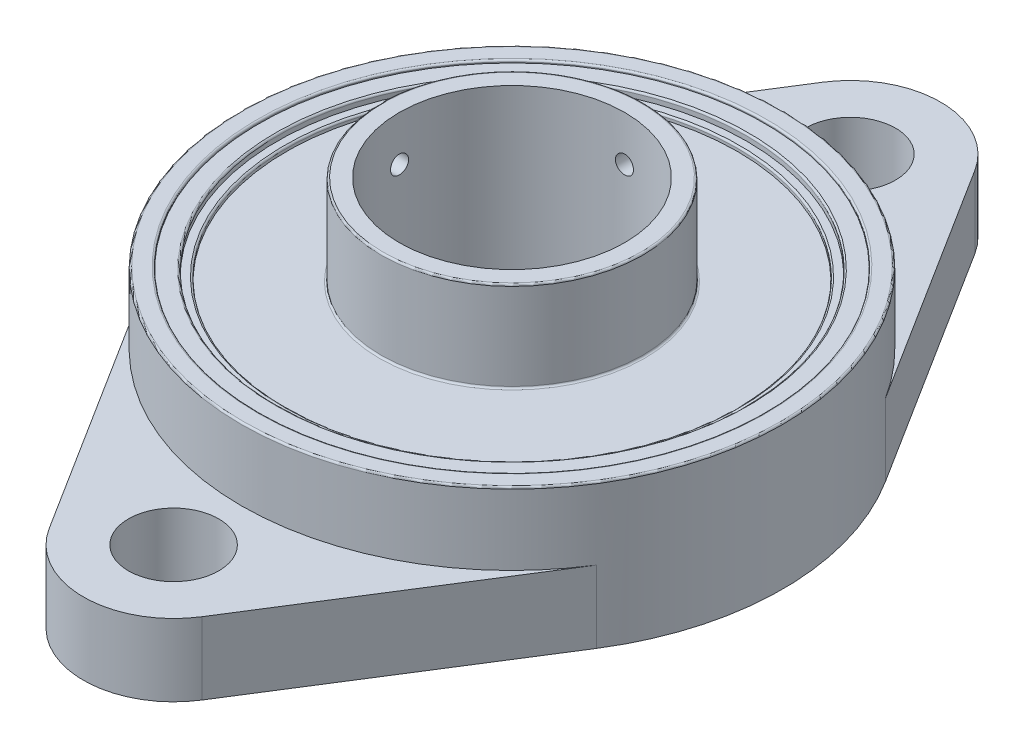
SolidWorks part; units mm, degrees
ref_plane "Front Plane" through (0, 0, 0) normal (0, 0, 1) x (1, 0, 0)
ref_plane "Top Plane" through (0, 0, 0) normal (0, 1, 0) x (1, 0, 0)
ref_plane "Right Plane" through (0, 0, 0) normal (1, 0, 0) x (0, 0, -1)
sketch "Sketch1" plane through (0, 0, 0) normal (0, 1, 0) x (1, 0, 0)
  line L0 (0, -47.5) -> (0, 47.5) construction
  line L1 (0, 0) -> (-50000, 0) construction
  line L2 (25.3772, -16) -> (8.4591, -42.8333)
  line L3 (25.3772, 16) -> (8.4591, 42.8333)
  line L4 (-25.3772, -16) -> (-8.4591, -42.8333)
  line L5 (-25.3772, 16) -> (-8.4591, 42.8333)
  circle A0 centre (0, 0) radius 30
  circle A1 centre (0, 0) radius 12.5
  circle A2 centre (0, 37.5) radius 5
  circle A3 centre (0, 0) radius 28
  circle A4 centre (0, 0) radius 14.5
  arc A5 (8.4591, 42.8333) -> (-8.4591, 42.8333) centre (0, 37.5) ccw
  circle A6 centre (0, -37.5) radius 5
  arc A7 (-8.4591, -42.8333) -> (8.4591, -42.8333) centre (0, -37.5) ccw
  circle A8 centre (0, 0) radius 26
  circle A9 centre (0, 0) radius 25
  point P6 (0, 0)
  dimension "D1" = 25
  dimension "D2" = 60
  dimension "D5" = 10
  dimension "D3" = 95
  dimension "D4" = 75
  dimension "D6" = 2
  dimension "D7" = 2
  dimension "D8" = 2
  dimension "D9" = 1
extrude "A1" add sketch "Sketch1" along normal blind 8 contours L4 A7 L2 A0 A6 | A0 A3 | L3 A5 L5 A0 A2 region at (16.4128, 0, 29.0981) region at (0, 0, 29.1515) region at (-16.4128, 0, -29.0981)
extrude "A" add sketch "Sketch1<3>" along normal blind 16 contours A0 A3 region at (0, 0, 29.1515)
sketch "Sketch1<3>" plane through (0, 0, 0) normal (0, 1, 0) x (1, 0, 0) same geometry as "Sketch1"
extrude "A0" add sketch "Sketch1<4>" along normal blind 24.5 contours A4 A1 region at (-14.0899, 0, 0)
sketch "Sketch1<4>" plane through (0, 0, 0) normal (0, 1, 0) x (1, 0, 0) same geometry as "Sketch1"
extrude "Bearing outer d" add sketch "Sketch1<7>" along normal blind 13 from offset 2 separate body contours A8 A9 region at (-25.2646, 0, 0)
sketch "Sketch1<7>" plane through (0, 0, 0) normal (0, 1, 0) x (1, 0, 0) same geometry as "Sketch1"
extrude "Boss-Extrude6" add sketch "Sketch1<8>" along normal blind 14.5 from offset 1.2 contours A3 A8 region at (-27.208, 0, 0)
sketch "Sketch1<8>" plane through (0, 0, 0) normal (0, 1, 0) x (1, 0, 0) same geometry as "Sketch1"
extrude "Boss-Extrude7" add sketch "Sketch1<9>" along normal blind 13 from offset 1.5 contours A9 A4 region at (-24.2929, 0, 0)
sketch "Sketch1<9>" plane through (0, 0, 0) normal (0, 1, 0) x (1, 0, 0) same geometry as "Sketch1"
sketch "Sketch2" plane through (0, 0, 0) normal (1, 0, 0) x (0, 0, -1)
  line L0 (0, 0) -> (0, 50000) construction
  line L1 (-16, 0) -> (16, 0) construction
  line L2 (14.5, 19.5) -> (-14.5, 19.5) construction
  line L3 (14.5, 14.5) -> (14.5, 24.5) construction
  line L4 (-14.5, 24.5) -> (-14.5, 14.5) construction
  circle A0 centre (0, 19.5) radius 1
  point P4 (0, 0)
  dimension "D1" = 2
extrude "Cut-Extrude1" cut sketch "Sketch2" against normal up to next
sketch "Sketch3" plane through (0, 0, 0) normal (0, 0, 1) x (1, 0, 0)
  line L0 (0, 0) -> (0, 50000) construction
  line L1 (6, 19.5) -> (-49994, 19.5) construction
  line L3 (14.5, 14.5) -> (14.5, 24.5) construction
  circle A0 centre (0, 19.5) radius 1
  point P7 (14.5, 19.5)
  point P10 (0, 9.9)
  dimension "D1" = 2
extrude "Cut-Extrude2" cut sketch "Sketch3" against normal up to next
fillet "Fillet1" radius 0.2 1 edges at (0, 15, 25)
fillet "Fillet2" radius 0.2 5 edges at (0, 24.5, 14.5) (0, 14.5, 14.5) (0, 16, 30) (0, 16, 28) (0, 15.7, 26)
equation "\"A\"= \"D1@A\""
equation "\"A0\"= \"D1@A0\""
equation "\"A1\"= \"D1@A1\""
equation "\"D1@Bearing outer d\"=\"D1@Boss-Extrude6\" - 1.5"
equation "\"D1@Boss-Extrude6\"=\"D1@A\" - 1.5"
equation "\"D1@Boss-Extrude7\"= \"D1@Bearing outer d\""
equation "\"S\"= \"D19@Boss-Extrude7\""
equation "\"D19@Boss-Extrude6\"=\"D19@Boss-Extrude7\" - 0.3"
equation "\"H\"= \"D3@Sketch1\""
equation "\"J\"= \"D4@Sketch1\""
equation "\"L\"= \"D2@Sketch1\""
equation "\"N\"= \"D5@Sketch1\""
equation "\"d\"= \"D1@Sketch1\""
